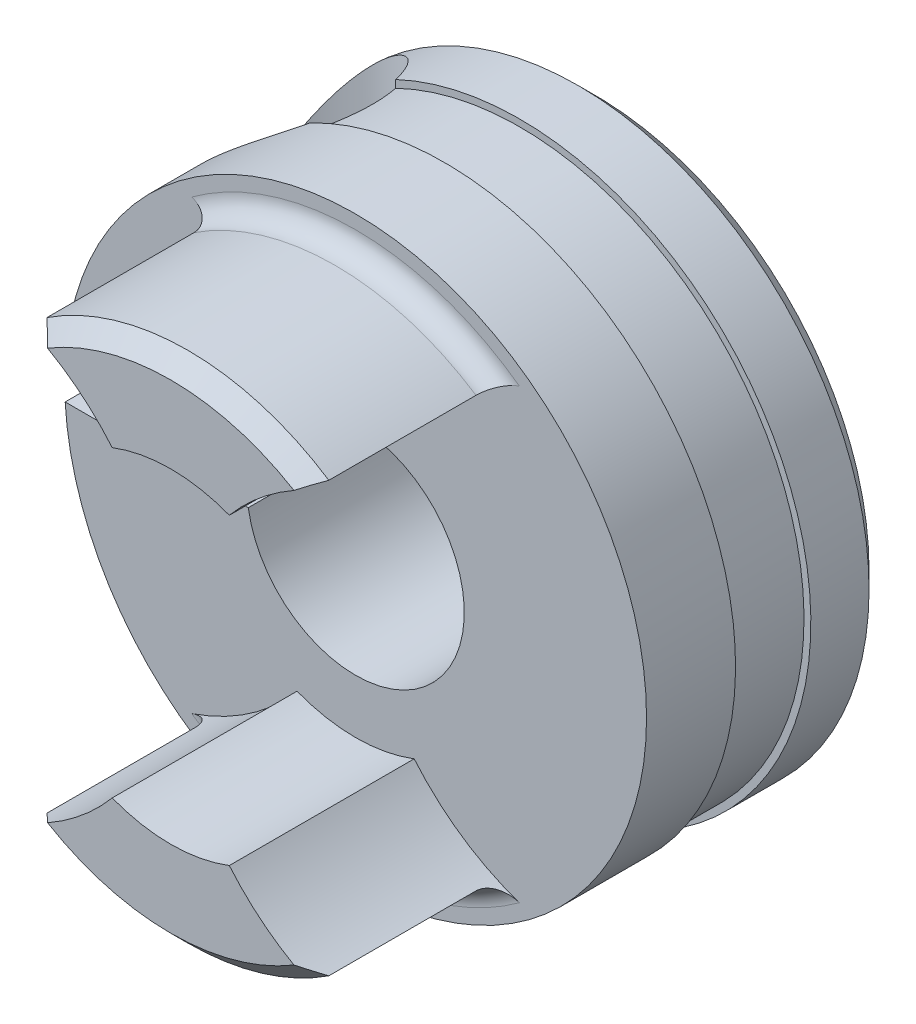
SolidWorks part; units mm, degrees
ref_plane "Front Plane" through (0, 0, 0) normal (0, 0, 1) x (1, 0, 0)
ref_plane "Top Plane" through (0, 0, 0) normal (0, 1, 0) x (1, 0, 0)
ref_plane "Right Plane" through (0, 0, 0) normal (1, 0, 0) x (0, 0, -1)
sketch "Sketch1" plane through (0, 0, 0) normal (1, 0, 0) x (0, 0, -1)
  line L0 (-12.4, 7) -> (-12.4, 3.675)
  line L1 (-12.4, 3.675) -> (-11.9, 3.175)
  line L2 (-11.9, 3.175) -> (-0.5, 3.175)
  line L3 (-0.5, 3.175) -> (0, 3.675)
  line L4 (0, 3.675) -> (0, 8)
  line L5 (0, 8) -> (-0.5, 8.5)
  line L6 (-0.5, 8.5) -> (-2.2, 8.5)
  line L7 (-2.2, 8.5) -> (-2.2, 8.3)
  line L8 (-2.2, 8.3) -> (-4.4, 8.3)
  line L9 (-4.4, 8.3) -> (-4.4, 8.5)
  line L10 (-4.4, 8.5) -> (-7, 8.5)
  line L11 (-7, 8.5) -> (-7, 8.1)
  line L12 (-7.6, 7.5) -> (-11.9, 7.5)
  line L13 (-11.9, 7.5) -> (-12.4, 7)
  line L14 (0, 0) -> (-12.4, 0) construction
  arc A0 (-7, 8.1) -> (-7.6, 7.5) centre (-7.6, 8.1) cw
revolve "Revolve1" add sketch "Sketch1" angle 360 about L14 reverse direction yes
ref_plane "Plane1" through (0, 0, 3) normal (0, 0, 1) x (1, 0, 0)
sketch "Sketch2" plane through (0, 0, 3) normal (0, 0, 1) x (1, 0, 0)
  line L0 (-6, 8.5) -> (-3.5, 8.5)
  line L1 (-3.5, 8.5) -> (-3.5, 2.3)
  line L2 (-3.5, 2.3) -> (-4.9935, 2.3)
  line L3 (-4.9935, 2.3) -> (-4.9935, -8.5)
  line L4 (-4.9935, -8.5) -> (-6, -8.5)
  line L5 (-6, -8.5) -> (-6, 8.5)
  line L6 (-6, -8.5) -> (-6, 8.5) construction
revolve "Cut-Revolve1" cut sketch "Sketch2" angle 360 about L6 reverse direction yes
cosmetic thread "Cosmetic Thread1"
sketch "Sketch3" plane through (0, 0, 0) normal (0, 0, 1) x (1, 0, 0)
  line L0 (-8.5, 0.5) -> (-8.5, -0.5)
  line L1 (-8.5, -0.5) -> (0, -0.5)
  line L2 (0, -0.5) -> (0, 0.5)
  line L3 (0, 0.5) -> (-8.5, 0.5)
extrude "Cut-Extrude1" cut sketch "Sketch3" along normal blind 12.4
ref_plane "Plane2" through (0, 0, 7) normal (0, 0, 1) x (1, 0, 0)
sketch "Sketch4" plane through (0, 0, 7) normal (0, 0, 1) x (1, 0, 0)
  arc A0 (-1.7109, 4.4312) -> (-1.7109, -4.4312) centre (-7, 0) ccw
  arc A1 (-1.7109, -4.4312) -> (1.7109, -4.4312) centre (0, 0) ccw
  arc A2 (1.7109, -4.4312) -> (1.7109, 4.4312) centre (7, 0) ccw
  arc A3 (1.7109, 4.4312) -> (-1.7109, 4.4312) centre (0, 0) ccw
extrude "Cut-Extrude2" cut sketch "Sketch4" along normal blind 12.4
ref_plane "Plane3" through (0, 2.3, 0) normal (0, 1, 0) x (1, 0, 0)
ref_plane "ANBAU XY" through (0, 0, 0) normal (0, 0, 1) x (1, 0, 0)
ref_plane "ANBAU XZ" through (0, 0, 0) normal (0, -1, 0) x (-1, 0, 0)
ref_plane "ANBAU YZ" through (0, 0, 0) normal (1, 0, 0) x (0, 0, -1)
ref_axis "ANBAU X" through (-80.9, 0, 0) along (1, 0, 0)
ref_axis "ANBAU Y" through (0, -50, 0) along (0, 1, 0)
ref_axis "ANBAU Z" through (0, 0, 80.9) along (0, 0, -1)
sketch3d "ANBAU"
  point P0 (0, 0, 0)
ref_plane "R XY" through (0, 0, 7) normal (0, 0, 1) x (1, 0, 0)
ref_plane "R XZ" through (0, 0, 0) normal (0, -1, 0) x (-1, 0, 0)
ref_plane "R YZ" through (0, 0, 0) normal (1, 0, 0) x (0, 0, -1)
ref_axis "R X" through (-80.9, 0, 7) along (1, 0, 0)
ref_axis "R Y" through (0, -50, 7) along (0, 1, 0)
ref_axis "R Z" through (0, 0, 80.9) along (0, 0, -1)
sketch3d "R"
  point P0 (0, 0, 7)
ref_plane "S XY" through (0, 2.3, 0) normal (0, 1, 0) x (1, 0, 0)
ref_plane "S XZ" through (0, 0, 3) normal (0, 0, 1) x (1, 0, 0)
ref_plane "S YZ" through (-6, 0, 0) normal (1, 0, 0) x (0, 0, -1)
ref_axis "S X" through (-80.9, 2.3, 3) along (1, 0, 0)
ref_axis "S Y" through (-6, 2.3, 50) along (0, 0, -1)
ref_axis "S Z" through (-6, 50, 3) along (0, -1, 0)
sketch3d "S"
  point P0 (-6, 2.3, 3)
other "Freeze***"
